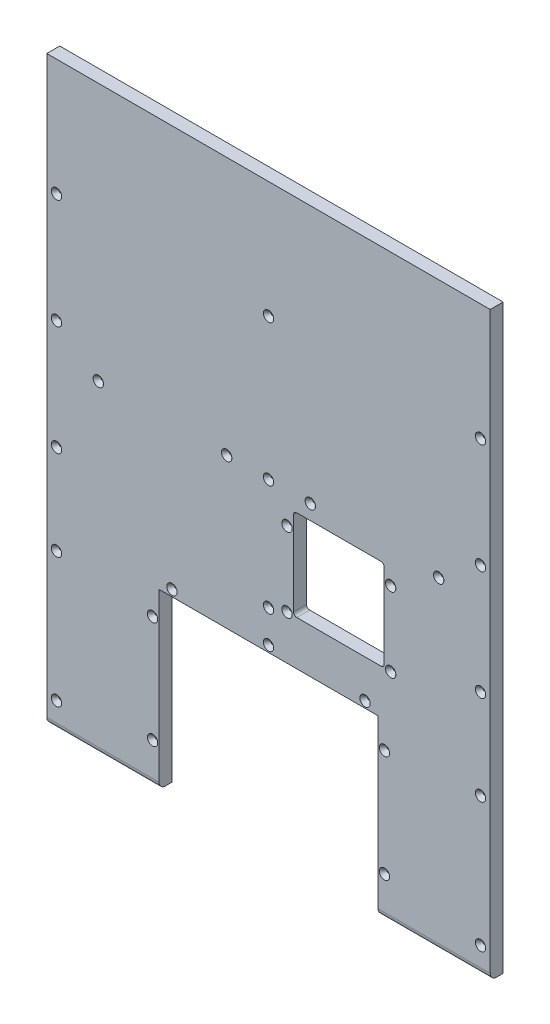
SolidWorks part; units mm, degrees
material "Beech"
ref_plane "Front Plane" through (0, 0, 0) normal (0, 0, 1) x (1, 0, 0)
ref_plane "Top Plane" through (0, 0, 0) normal (0, 1, 0) x (1, 0, 0)
ref_plane "Right Plane" through (0, 0, 0) normal (1, 0, 0) x (0, 0, -1)
sketch "Sketch1" plane through (0, 0, 0) normal (0, 0, 1) x (1, 0, 0)
  line L0 (124.0045, -60.2629) -> (124.0045, 250.6666) construction
  line L1 (16.7045, -230.2629) -> (-93.2955, -230.2629)
  line L2 (16.7045, -60.2629) -> (16.7045, -230.2629)
  line L3 (-93.2955, -230.2629) -> (-93.2955, 250.6666)
  line L16 (341.3045, -230.2629) -> (341.3045, 250.6666)
  line L17 (341.3045, 250.6666) -> (-93.2955, 250.6666)
  line L21 (16.7045, -60.2629) -> (231.3045, -60.2629)
  line L22 (231.3045, -60.2629) -> (231.3045, -230.2629)
  line L23 (231.3045, -230.2629) -> (341.3045, -230.2629)
  dimension "D1" = 434.6
  dimension "D2" = 480.9295
  dimension "D3" = 110
  dimension "D4" = 170
extrude "Boss-Extrude1" add sketch "Sketch1" against normal blind 12.7
fillet "Fillet1" radius 6.35 2 edges at (286.3045, -230.2629, 0) (-38.2955, -230.2629, 0)
hole_wizard "Hole1" positions "Sketch2" profile "Sketch3" legacy end condition through all
sketch "Sketch2" plane through (0, 0, 0) normal (0, 0, 1) x (1, 0, 0)
  line L8 (331.7795, 250.6666) -> (331.7795, -230.2629) construction
  line L9 (341.3045, 250.6666) -> (-93.2955, 250.6666) construction
  line L12 (322.2545, 226.323) -> (322.2545, -204.8629) construction
  line L13 (341.3045, -204.8629) -> (341.3045, 226.323) construction
  line L15 (331.7795, 225.2666) -> (331.7795, 10.2019)
  line L16 (331.7795, 10.2019) -> (331.7795, -204.8629)
  line L17 (133.5295, 86.6832) -> (322.2545, 86.6832) construction
  line L19 (322.2545, 96.2082) -> (133.5295, 96.2082) construction
  line L20 (133.5295, 77.1582) -> (322.2545, 77.1582) construction
  line L21 (133.5295, -47.5629) -> (133.5295, 259.4032) construction
  line L22 (322.2545, 259.4032) -> (322.2545, -217.5629) construction
  line L23 (133.5295, 86.6832) -> (196.4378, 86.6832)
  line L24 (196.4378, 86.6832) -> (259.3461, 86.6832)
  line L25 (259.3461, 86.6832) -> (322.2545, 86.6832)
  line L26 (341.3045, -230.2629) -> (231.3045, -230.2629) construction
  line L27 (237.6545, -60.2629) -> (237.6545, -217.5629) construction
  line L31 (237.6545, -60.2629) -> (237.6545, -112.6962)
  line L32 (237.6545, -112.6962) -> (237.6545, -165.1295)
  line L33 (237.6545, -165.1295) -> (237.6545, -217.5629)
  line L34 (124.0045, 250.6666) -> (124.0045, -47.5629) construction
  line L36 (114.4795, 226.323) -> (114.4795, -49.1129) construction
  line L37 (133.5295, -49.1129) -> (133.5295, 226.323) construction
  line L38 (4.0045, -53.9129) -> (244.0045, -53.9129) construction
  line L40 (4.0045, -47.5629) -> (244.0045, -47.5629) construction
  line L41 (4.0045, -60.2629) -> (244.0045, -60.2629) construction
  line L42 (4.0045, -60.2629) -> (4.0045, -47.5629) construction
  line L43 (244.0045, -47.5629) -> (244.0045, -60.2629) construction
  point P29 (331.7795, -204.8629)
  point P32 (331.7795, 10.2019)
  point P34 (331.7795, 225.2666)
  point P54 (331.7795, 117.7343)
  point P61 (331.7795, -77.8629)
  point P87 (164.9836, 86.6832)
  point P89 (290.8003, 86.6832)
  point P118 (237.6545, -86.4795)
  point P120 (237.6545, -191.3462)
  point P143 (124.0045, 86.6832)
  point P145 (124.0045, 225.2666)
  point P147 (124.0045, -22.1629)
  point P151 (10.3545, -191.3462)
  point P152 (10.3545, -86.4795)
  point P153 (-42.7914, 86.6832)
  point P154 (83.0253, 86.6832)
  point P155 (-83.7705, -77.8629)
  point P156 (-83.7705, 117.7343)
  point P157 (-83.7705, 225.2666)
  point P158 (-83.7705, 10.2019)
  point P159 (-83.7705, -204.8629)
  point P174 (124.0045, -53.9129)
  point P176 (29.4045, -53.9129)
  point P178 (218.6045, -53.9129)
  dimension "D1" = 25.4
  dimension "D2" = 127
  dimension "D3" = 25.4
  dimension "D4" = 25.4
  dimension "D5" = 25.4
  dimension "D6" = 25.4
  dimension "D7" = 25.4
sketch "Sketch3" plane through (218.6045, -53.9129, 0) normal (1, 0, 0) x (0, -1, 0)
  line L0 (0, 0) -> (0, 13.6539)
  line L1 (0, 13.6539) -> (1.5875, 12.7)
  line L2 (1.5875, 12.7) -> (1.5875, 4.0177)
  line L3 (1.5875, 4.0177) -> (5.08, 0)
  line L4 (5.08, 0) -> (0, 0)
  line L5 (0, -14.3089) -> (0, 102.4216) construction
  line L6 (0, 13.6539) -> (-1.5875, 12.7) construction
  line L7 (-1.5875, 4.0177) -> (-5.08, 0) construction
  dimension "Diameter" = 3.175
  dimension "Depth" = 12.7
  dimension "C-Sink Diameter" = 10.16
  dimension "C-Sink Angle" = 82
  dimension "Drill Angle" = 118
hole_wizard "Hole2" positions "Sketch4" profile "Sketch5" legacy
sketch "Sketch4" plane through (124.0045, -215.2871, 0) normal (0, 0, 1) x (1, 0, 0)
  line L1 (0, 465.9538) -> (0, 167.7243) construction
  point P1 (113.65, 128.8076)
  point P3 (113.65, 23.941)
  point P5 (-94.6, 161.3743)
  point P7 (94.6, 161.3743)
  point P9 (0, 161.3743)
  point P11 (0, 193.1243)
  point P13 (0, 440.5538)
  point P15 (0, 301.9704)
  point P17 (40.9792, 301.9704)
  point P19 (166.7958, 301.9704)
  point P21 (207.775, 440.5538)
  point P23 (207.775, 333.0214)
  point P25 (207.775, 225.489)
  point P27 (207.775, 137.4243)
  point P29 (207.775, 10.4243)
  point P33 (-207.775, 10.4243)
  point P34 (-207.775, 137.4243)
  point P35 (-207.775, 225.489)
  point P36 (-207.775, 333.0214)
  point P37 (-207.775, 440.5538)
  point P38 (-166.7958, 301.9704)
  point P39 (-40.9792, 301.9704)
  point P40 (-113.65, 23.941)
  point P41 (-113.65, 128.8076)
sketch "Sketch5" plane through (237.6545, -86.4795, 0) normal (1, 0, 0) x (0, -1, 0)
  line L0 (0, 0) -> (0, 32.7039)
  line L1 (0, 32.7039) -> (1.5875, 31.75)
  line L2 (1.5875, 31.75) -> (1.5875, 4.0177)
  line L3 (1.5875, 4.0177) -> (5.08, 0)
  line L4 (5.08, 0) -> (0, 0)
  line L5 (0, -14.3089) -> (0, 102.4216) construction
  line L6 (0, 32.7039) -> (-1.5875, 31.75) construction
  line L7 (-1.5875, 4.0177) -> (-5.08, 0) construction
  dimension "Diameter" = 3.175
  dimension "Depth" = 31.75
  dimension "C-Sink Diameter" = 10.16
  dimension "C-Sink Angle" = 82
  dimension "Drill Angle" = 118
sketch "Sketch6" plane through (0, 0, 0) normal (0, 0, 1) x (1, 0, 0)
  line L0 (215.1525, 5.5432) -> (170.7025, 49.9932) construction
  line L2 (237.3775, 72.2182) -> (148.4775, 72.2182)
  line L3 (237.3775, 72.2182) -> (237.3775, -16.6818)
  line L4 (237.3775, -16.6818) -> (148.4775, -16.6818)
  line L5 (148.4775, 72.2182) -> (148.4775, -16.6818)
  line L6 (237.3775, 72.2182) -> (148.4775, -16.6818) construction
  line L7 (237.3775, -16.6818) -> (148.4775, 72.2182) construction
  point P4 (192.9275, 27.7682)
  point P9 (192.9275, 27.7682)
  dimension "D1" = 88.9
extrude "Cut-Extrude1" cut sketch "Sketch6" against normal up to next
fillet "Fillet2" radius 3.175 4 edges at (148.4775, 72.2182, -6.35) (148.4775, -16.6818, -6.35) (237.3775, -16.6818, -6.35) (237.3775, 72.2182, -6.35)
hole_wizard "Hole3" positions "Sketch7" profile "Sketch8" legacy
sketch "Sketch7" plane through (124.0045, -126.3871, 0) normal (0, 0, 1) x (1, 0, 0)
  line L1 (0, 465.9538) -> (0, 66.1243) construction
  line L2 (126.073, 146.2179) -> (113.373, 146.2179) construction
  line L6 (119.723, 195.4304) -> (119.723, 97.0054) construction
  line L10 (68.923, 196.0654) -> (68.923, 112.2454) construction
  point P1 (113.65, 39.9076)
  point P3 (113.65, -64.959)
  point P5 (-94.6, 72.4743)
  point P7 (94.6, 72.4743)
  point P9 (0, 72.4743)
  point P11 (0, 104.2243)
  point P13 (0, 351.6538)
  point P15 (0, 213.0704)
  point P17 (40.9792, 213.0704)
  point P19 (166.7958, 213.0704)
  point P21 (207.775, 351.6538)
  point P23 (207.775, 244.1214)
  point P25 (207.775, 136.589)
  point P27 (207.775, 48.5243)
  point P29 (207.775, -78.4757)
  point P33 (-207.775, -78.4757)
  point P34 (-207.775, 48.5243)
  point P35 (-207.775, 136.589)
  point P36 (-207.775, 244.1214)
  point P37 (-207.775, 351.6538)
  point P38 (-166.7958, 213.0704)
  point P39 (-40.9792, 213.0704)
  point P40 (-113.65, -64.959)
  point P41 (-113.65, 39.9076)
  point P65 (119.723, 109.7054)
  point P68 (119.723, 182.7304)
  point P78 (18.123, 109.7054)
  point P79 (18.123, 182.7304)
  point P81 (0, 0)
  point P82 (113.65, 23.941)
  point P83 (0, 0)
  point P84 (207.775, -78.2752)
  point P85 (209.3058, -90.1558)
  point P86 (207.775, -78.4757)
  point P88 (113.65, -64.959)
  point P90 (207.775, 48.5243)
  point P92 (0, 0)
  point P93 (207.775, 136.589)
  point P95 (207.775, 244.1214)
  point P97 (207.775, 351.6538)
  point P99 (113.65, 39.9076)
  point P101 (94.6, 72.4743)
  point P103 (0, 72.4743)
  point P105 (0, 104.2243)
  point P107 (0, 0)
  point P108 (0, 213.0704)
  point P110 (0, 0)
  point P111 (0, 351.6538)
  point P113 (-40.9792, 213.0704)
  point P115 (-94.6, 72.4743)
  point P117 (-166.7958, 213.0704)
  point P119 (-113.65, -64.959)
  point P121 (0, 66.1243)
  point P124 (68.923, 112.2454)
sketch "Sketch8" plane through (237.6545, -86.4795, 0) normal (1, 0, 0) x (0, -1, 0)
  line L0 (0, 0) -> (0, 32.7039)
  line L1 (0, 32.7039) -> (1.5875, 31.75)
  line L2 (1.5875, 31.75) -> (1.5875, 4.0177)
  line L3 (1.5875, 4.0177) -> (5.08, 0)
  line L4 (5.08, 0) -> (0, 0)
  line L5 (0, -14.3089) -> (0, 102.4216) construction
  line L6 (0, 32.7039) -> (-1.5875, 31.75) construction
  line L7 (-1.5875, 4.0177) -> (-5.08, 0) construction
  dimension "Diameter" = 3.175
  dimension "Depth" = 31.75
  dimension "C-Sink Diameter" = 10.16
  dimension "C-Sink Angle" = 82
  dimension "Drill Angle" = 118
sketch "Sketch9" plane through (0, 250.6666, 0) normal (0, 1, 0) x (1, 0, 0)
  line L4 (-93.2955, 0) -> (341.3045, 0)
  line L5 (341.3045, 0) -> (341.3045, 12.7)
  line L6 (341.3045, 12.7) -> (-93.2955, 12.7)
  line L7 (-93.2955, 12.7) -> (-93.2955, 0)
  line L8 (-93.2955, 0) -> (341.3045, 0)
  line L9 (341.3045, 0) -> (341.3045, 12.7)
  line L10 (341.3045, 12.7) -> (-93.2955, 12.7)
  line L11 (-93.2955, 12.7) -> (-93.2955, 0)
  dimension "D1" = 0
extrude "Boss-Extrude2" add sketch "Sketch9" along normal blind 88.9
